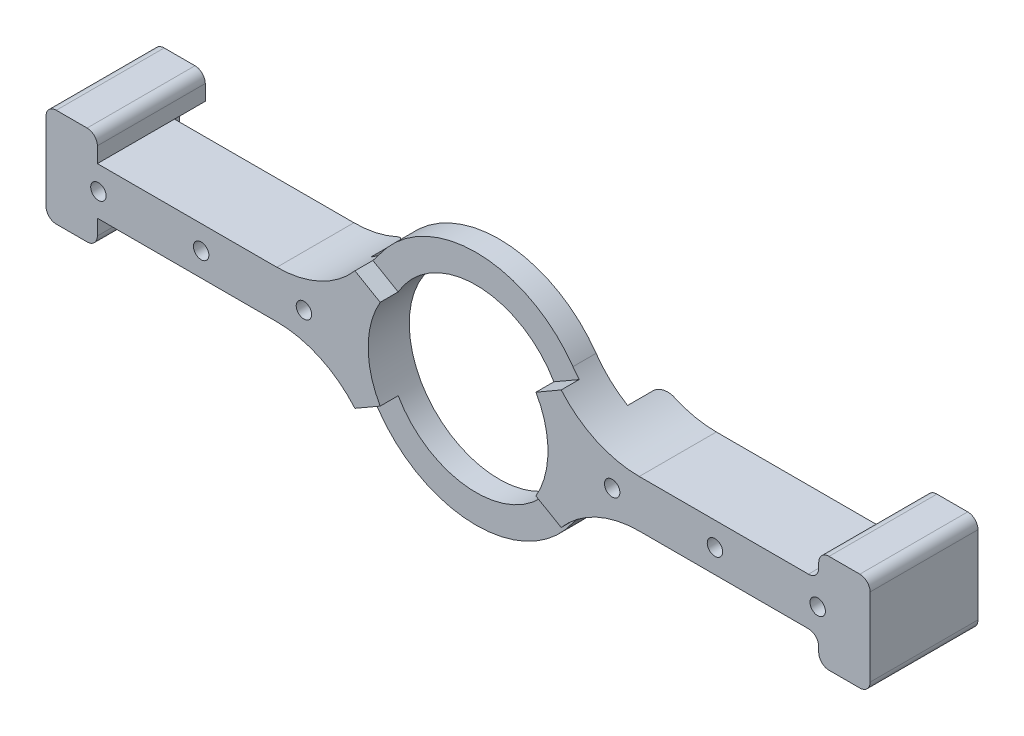
SolidWorks part; units mm, degrees
ref_plane "前视基准面" through (0, 0, 0) normal (0, 0, 1) x (1, 0, 0)
ref_plane "上视基准面" through (0, 0, 0) normal (0, 1, 0) x (1, 0, 0)
ref_plane "右视基准面" through (0, 0, 0) normal (1, 0, 0) x (0, 0, -1)
other "Configuration Table"
sketch "草图1" plane through (0, 0, 0) normal (0, 0, 1) x (1, 0, 0)
  line L0 (22.5353, 4.6) -> (75.2, 4.6)
  line L1 (-75.2, -4.6) -> (-22.5353, -4.6)
  line L2 (-75.2, -4.6) -> (-75.2, 4.6)
  line L3 (-75.2, 4.6) -> (-22.5353, 4.6)
  line L4 (75.2, -4.6) -> (75.2, 4.6)
  line L5 (-75.2, -4.6) -> (75.2, 4.6) construction
  line L6 (-75.2, 4.6) -> (75.2, -4.6) construction
  line L7 (22.5353, -4.6) -> (75.2, -4.6)
  line L8 (-70, 0) -> (-75.2, 0) construction
  circle A0 centre (0, 20.75) radius 1.5 construction
  circle A1 centre (14.6725, 14.6725) radius 1.5 construction
  circle A2 centre (20.75, 0) radius 1.5 construction
  circle A3 centre (14.6725, -14.6725) radius 1.5 construction
  circle A4 centre (0, -20.75) radius 1.5 construction
  circle A5 centre (-14.6725, -14.6725) radius 1.5 construction
  circle A6 centre (-20.75, 0) radius 1.5 construction
  circle A7 centre (-14.6725, 14.6725) radius 1.5 construction
  circle A8 centre (0, 0) radius 17.5
  circle A9 centre (0, 0) radius 23 construction
  arc A10 (-22.5353, 4.6) -> (22.5353, 4.6) centre (0, 0) cw
  arc A11 (22.5353, -4.6) -> (-22.5353, -4.6) centre (0, 0) cw
  circle A12 centre (-70, 0) radius 1.5
  circle A13 centre (-50, 0) radius 1.5
  circle A14 centre (-30, 0) radius 1.5
  circle A15 centre (-10, 0) radius 1.5 construction
  circle A17 centre (30, 0) radius 1.5
  circle A18 centre (50, 0) radius 1.5
  circle A19 centre (70, 0) radius 1.5
  circle A21 centre (10, 0) radius 1.5
  circle A22 centre (90, 0) radius 1.5
  point P19 (0, 0)
  point P25 (22.5353, 4.6)
  point P26 (22.5353, -4.6)
  point P27 (-22.5353, 4.6)
  point P28 (-22.5353, -4.6)
  dimension "D2" = 3
  dimension "D4" = 35
  dimension "D5" = 46
  dimension "D8" = 3
  dimension "D1" = 20.75
  dimension "D3" = 8
  dimension "D6" = 9.2
  dimension "D7" = 150.4
  dimension "D9" = 5.2
  dimension "D11" = 20
  dimension "D10" = 9
extrude "凸台-拉伸1" add sketch "草图1" along normal blind 8
sketch "草图2" plane through (0, 0, 8) normal (0, 0, 1) x (1, 0, 0)
  line L0 (-75.2, 0) -> (75.2, 0) construction
  line L1 (-19.9186, 11.5) -> (0, 0)
  line L2 (0, 0) -> (19.9186, 11.5)
  line L3 (0, 23) -> (0, 0) construction
  line L4 (0, 0) -> (19.9186, -11.5)
  line L5 (-19.9186, -11.5) -> (0, 0)
  line L6 (75.2, -4.6) -> (75.2, 4.6)
  line L7 (75.2, 4.6) -> (22.5353, 4.6)
  line L8 (-22.5353, 4.6) -> (-75.2, 4.6)
  line L9 (-75.2, 4.6) -> (-75.2, -4.6)
  line L10 (-75.2, -4.6) -> (-22.5353, -4.6)
  line L11 (22.5353, -4.6) -> (75.2, -4.6)
  line L12 (75.2, -4.6) -> (75.2, 4.6)
  line L13 (75.2, 4.6) -> (22.5353, 4.6)
  line L14 (-22.5353, 4.6) -> (-75.2, 4.6)
  line L15 (-75.2, 4.6) -> (-75.2, -4.6)
  line L16 (-75.2, -4.6) -> (-22.5353, -4.6)
  line L17 (22.5353, -4.6) -> (75.2, -4.6)
  circle A0 centre (0, 0) radius 17.5 construction
  circle A1 centre (0, 0) radius 17.5
  arc A2 (22.5353, 4.6) -> (-22.5353, 4.6) centre (0, 0) ccw
  arc A3 (-22.5353, -4.6) -> (22.5353, -4.6) centre (0, 0) ccw
  arc A4 (22.5353, 4.6) -> (-22.5353, 4.6) centre (0, 0) ccw
  arc A5 (-22.5353, -4.6) -> (22.5353, -4.6) centre (0, 0) ccw
  dimension "D2" = 60
  dimension "D1" = 0
extrude "切除-拉伸1" cut sketch "草图2" against normal blind 3.5
fillet "圆角1" radius 20 4 edges at (-22.5353, -4.6, 4) (-22.5353, 4.6, 4) (22.5353, -4.6, 4) (22.5353, 4.6, 4)
sketch "草图3" plane through (0, 0, 0) normal (0, 0, -1) x (-1, 0, 0)
  line L0 (0, 23) -> (0, -23)
  line L1 (-25, 7.4371) -> (-25, -7.4371)
  line L2 (25, 7.4371) -> (25, -7.4371)
  line L6 (-75.2, 4.6) -> (-75.2, -4.6)
  line L7 (-75.2, -4.6) -> (-35.2681, -4.6)
  line L8 (35.2681, -4.6) -> (75.2, -4.6)
  line L9 (75.2, -4.6) -> (75.2, 4.6)
  line L10 (75.2, 4.6) -> (35.2681, 4.6)
  line L11 (-35.2681, 4.6) -> (-75.2, 4.6)
  line L12 (-75.2, 4.6) -> (-75.2, -4.6)
  line L13 (-75.2, -4.6) -> (-35.2681, -4.6)
  line L14 (35.2681, -4.6) -> (75.2, -4.6)
  line L15 (75.2, -4.6) -> (75.2, 4.6)
  line L16 (75.2, 4.6) -> (35.2681, 4.6)
  line L17 (-35.2681, 4.6) -> (-75.2, 4.6)
  arc A6 (-18.8643, -13.1581) -> (-35.2681, -4.6) centre (-35.2681, -24.6) ccw
  arc A7 (-18.8643, -13.1581) -> (18.8643, -13.1581) centre (0, 0) ccw
  arc A8 (35.2681, -4.6) -> (18.8643, -13.1581) centre (35.2681, -24.6) ccw
  arc A9 (18.8643, 13.1581) -> (35.2681, 4.6) centre (35.2681, 24.6) ccw
  arc A10 (18.8643, 13.1581) -> (-18.8643, 13.1581) centre (0, 0) ccw
  arc A11 (-35.2681, 4.6) -> (-18.8643, 13.1581) centre (-35.2681, 24.6) ccw
  arc A12 (-18.8643, -13.1581) -> (-35.2681, -4.6) centre (-35.2681, -24.6) ccw
  arc A13 (-18.8643, -13.1581) -> (18.8643, -13.1581) centre (0, 0) ccw
  arc A14 (35.2681, -4.6) -> (18.8643, -13.1581) centre (35.2681, -24.6) ccw
  arc A15 (18.8643, 13.1581) -> (35.2681, 4.6) centre (35.2681, 24.6) ccw
  arc A16 (18.8643, 13.1581) -> (-18.8643, 13.1581) centre (0, 0) ccw
  arc A17 (-35.2681, 4.6) -> (-18.8643, 13.1581) centre (-35.2681, 24.6) ccw
  dimension "D2" = 25
  dimension "D1" = 0
extrude "凸台-拉伸2" add sketch "草图3" along normal blind 7
sketch "草图4" plane through (0, 0, -7) normal (0, 0, -1) x (-1, 0, 0)
  line L0 (0, 23) -> (0, -23)
  line L1 (-70.2, 4.6) -> (-70.2, 9.6)
  line L2 (-70.2, 9.6) -> (-80.2, 9.6)
  line L3 (-80.2, 9.6) -> (-80.2, -9.6)
  line L4 (-80.2, -9.6) -> (-70.2, -9.6)
  line L5 (-25, -7.4371) -> (-25, 7.4371)
  line L6 (-35.2681, 4.6) -> (-75.2, 4.6)
  line L7 (-75.2, 4.6) -> (-75.2, -4.6)
  line L8 (-75.2, -4.6) -> (-35.2681, -4.6)
  line L9 (-25, -7.4371) -> (-25, 7.4371)
  line L10 (-35.2681, 4.6) -> (-75.2, 4.6)
  line L11 (-75.2, 4.6) -> (-75.2, -4.6)
  line L12 (-75.2, -4.6) -> (-35.2681, -4.6)
  line L13 (-70.2, -9.6) -> (-70.2, -4.6)
  line L14 (70.2, -9.6) -> (70.2, -4.6)
  line L15 (75.2, 4.6) -> (75.2, -4.6)
  line L16 (80.2, -9.6) -> (70.2, -9.6)
  line L17 (80.2, 9.6) -> (80.2, -9.6)
  line L18 (70.2, 9.6) -> (80.2, 9.6)
  line L19 (70.2, 4.6) -> (70.2, 9.6)
  line L24 (25, 7.4371) -> (25, -7.4371)
  line L25 (35.2681, -4.6) -> (75.2, -4.6)
  line L26 (75.2, -4.6) -> (75.2, 4.6)
  line L27 (75.2, 4.6) -> (35.2681, 4.6)
  line L28 (25, 7.4371) -> (25, -7.4371)
  line L29 (35.2681, -4.6) -> (75.2, -4.6)
  line L30 (75.2, -4.6) -> (75.2, 4.6)
  line L31 (75.2, 4.6) -> (35.2681, 4.6)
  arc A0 (18.8643, 13.1581) -> (-18.8643, 13.1581) centre (0, 0) ccw construction
  arc A1 (-18.8643, -13.1581) -> (18.8643, -13.1581) centre (0, 0) ccw construction
  arc A4 (-35.2681, 4.6) -> (-25, 7.4371) centre (-35.2681, 24.6) ccw
  arc A5 (-25, -7.4371) -> (-35.2681, -4.6) centre (-35.2681, -24.6) ccw
  arc A6 (-35.2681, 4.6) -> (-25, 7.4371) centre (-35.2681, 24.6) ccw
  arc A7 (-25, -7.4371) -> (-35.2681, -4.6) centre (-35.2681, -24.6) ccw
  arc A8 (25, 7.4371) -> (35.2681, 4.6) centre (35.2681, 24.6) ccw
  arc A9 (35.2681, -4.6) -> (25, -7.4371) centre (35.2681, -24.6) ccw
  arc A10 (25, 7.4371) -> (35.2681, 4.6) centre (35.2681, 24.6) ccw
  arc A11 (35.2681, -4.6) -> (25, -7.4371) centre (35.2681, -24.6) ccw
  line M12 (-35.2681, 4.6) -> (-75.2, 4.6)
  line M13 (-75.2, 4.6) -> (-75.2, -4.6)
  line M14 (-75.2, -4.6) -> (-35.2681, -4.6)
  dimension "D2" = 5
  dimension "D3" = 5
  dimension "D4" = 5
  dimension "D1" = 0
  dimension "D5" = 0
extrude "凸台-拉伸3" add sketch "草图4" along normal blind 6 and the other way up to surface contours L4 L13 L1 L2 L3 M14 M13 M12 | L31 L15 L29 L14 L16 L17 L18 L19 other way up to face at (71.5, 0, 8)
fillet "圆角2" radius 2 12 edges at (-70.2, -9.6, -2.5) (-80.2, -9.6, -2.5) (-80.2, 9.6, -2.5) (-70.2, 9.6, -2.5) (-25, 0, -7) (25, 0, -7) (70.2, 4.6, 0.5) (70.2, -4.6, 0.5) (70.2, -9.6, -2.5) (70.2, 9.6, -2.5) (80.2, -9.6, -2.5) (80.2, 9.6, -2.5)
sketch "折弯-线1" plane through (0, 0, 0) normal (0, 1, 0) x (1, 0, 0)
sketch "边界框1" plane through (0, 0, 0) normal (0, 1, 0) x (1, 0, 0)
